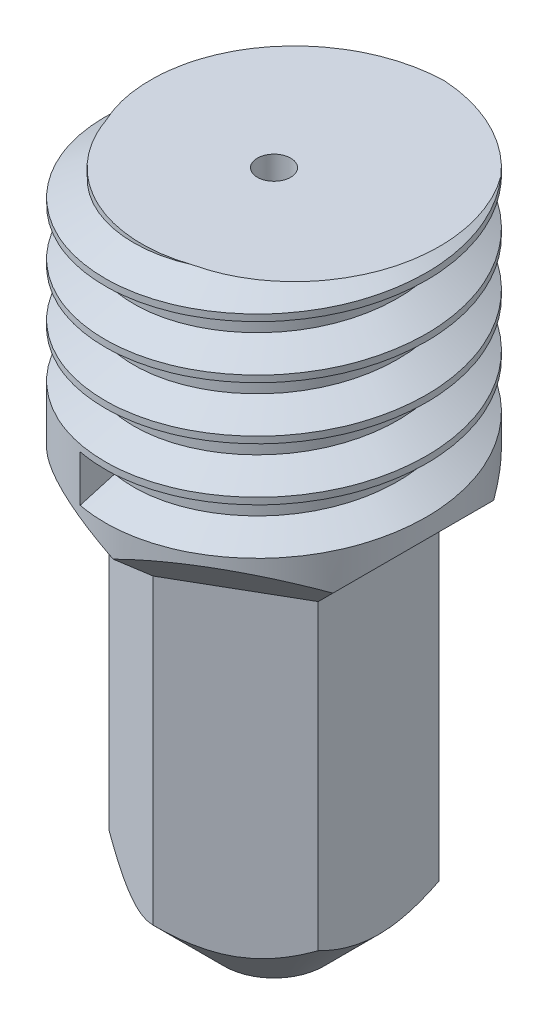
SolidWorks part; units mm, degrees
ref_plane "Front Plane" through (0, 0, 0) normal (0, 0, 1) x (1, 0, 0)
ref_plane "Top Plane" through (0, 0, 0) normal (0, 1, 0) x (1, 0, 0)
ref_plane "Right Plane" through (0, 0, 0) normal (1, 0, 0) x (0, 0, -1)
sketch "Sketch1" plane through (0, 0, 0) normal (0, 0, 1) x (1, 0, 0)
  line L0 (0, 0) -> (0, 7.2462) construction
  line L1 (-0.25, 10) -> (-0.25, 0)
  line L2 (-0.25, 0) -> (-0.75, 0)
  line L3 (-0.75, 0) -> (-1.813, 1.063)
  line L5 (-2.413, 10) -> (-0.25, 10)
  line L6 (-2.413, 7) -> (2.3687, 7) construction
  line L7 (-2.413, 10) -> (-2.413, 7)
  line L8 (-2.413, 7) -> (-1.813, 7)
  line L9 (-1.813, 7) -> (-1.813, 1.063)
  point P10 (-2.2086, 2.4565)
  point P12 (-1.6197, 0.8697)
  dimension "D1" = 0.6
  dimension "D2" = 0.25
  dimension "D3" = 0.5
  dimension "D4" = 45
  dimension "D5" = 10
  dimension "D6" = 7
  dimension "D7" = 2.413
revolve "Revolve1" add sketch "Sketch1" angle 360 about L0
sketch "Sketch2" plane through (0, 0, 0) normal (0, -1, 0) x (1, 0, 0)
  line L1 (0, 1.813) -> (-1.5701, 0.9065)
  line L2 (-1.5701, 0.9065) -> (-1.5701, -0.9065)
  line L3 (-1.5701, -0.9065) -> (0, -1.813)
  line L4 (0, -1.813) -> (1.5701, -0.9065)
  line L5 (1.5701, -0.9065) -> (1.5701, 0.9065)
  line L6 (1.5701, 0.9065) -> (0, 1.813)
  circle A0 centre (0, 0) radius 1.5701 construction
  circle A1 centre (0, 0) radius 1.813 construction
  circle A2 centre (0, 0) radius 1.813 construction
  point P1 (0, 0)
  point P10 (0, 1.3889)
extrude "Cut-Extrude1" cut sketch "Sketch2" against normal blind 7 flip side to cut
chamfer "Chamfer2" distance 1.4 angle 45 6 edges at (0.7851, 7, 1.3597) (-0.7851, 7, 1.3597) (-1.5701, 7, 0) (-0.7851, 7, -1.3598) (1.5701, 7, 0) (0.7851, 7, -1.3597)
thread "Thread2" pitch 0.7937 start angle 0, offset 1, length 3.8, pitch 0.7937, diameter 4.826
ref_plane "Plane2" through (-2.413, 11, 0) normal (0, 0, 1) x (-1, 0, 0)
sketch "Thread Profile2" plane through (-2.413, 11, 0) normal (0, 0, 1) x (-1, 0, 0)
  line L0 (0, 0) -> (0, 0.7937) construction
  line L11 (0, 0) -> (0, 0.6945)
  line L12 (0, 0.6945) -> (-0.4296, 0.4465)
  line L13 (-0.4296, 0.4465) -> (-0.4296, 0.248)
  line L15 (-0.4296, 0.248) -> (0, 0)
  line L17 (-0.4296, 0.3473) -> (0, 0.3473) construction
  point P2 (0, 0)
  dimension "Pitch" = 0.7937
  dimension "Profile_Angle" = 60
  dimension "Profile_Land" = 0.1984
  dimension "Profile_Height" = 0.4296
